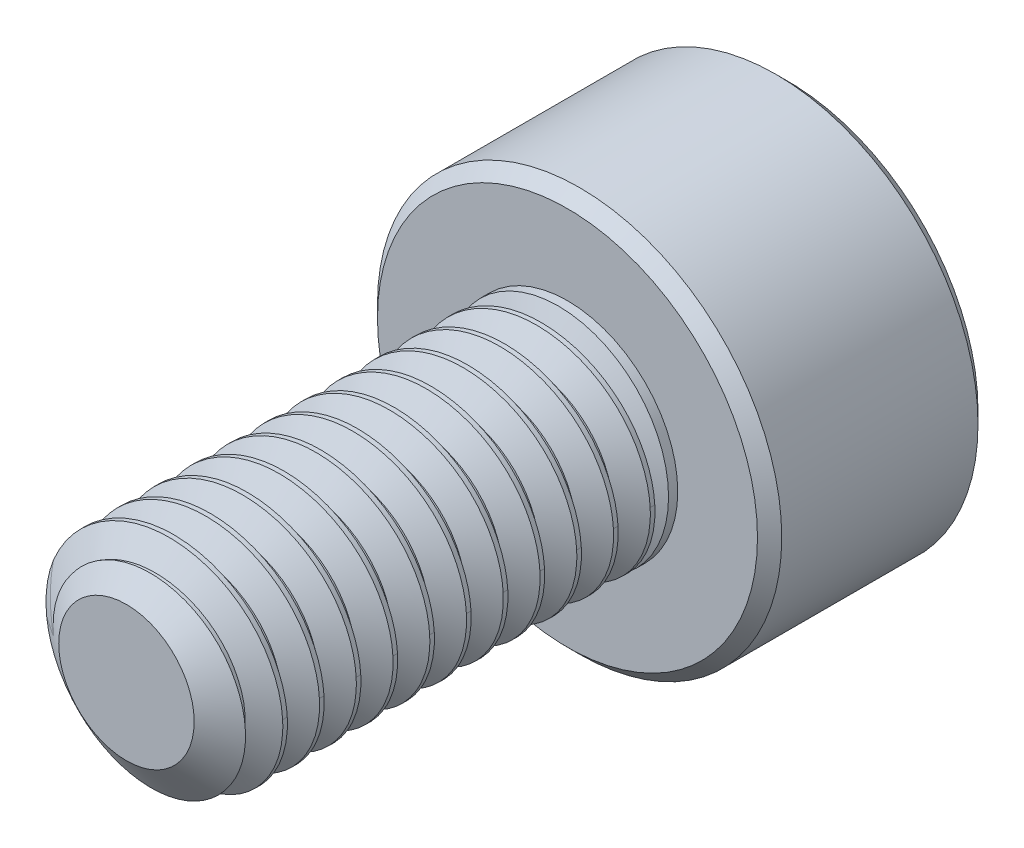
SolidWorks part; units mm, degrees
ref_plane "Front Plane" through (0, 0, 0) normal (0, 0, 1) x (1, 0, 0)
ref_plane "Top Plane" through (0, 0, 0) normal (0, 1, 0) x (1, 0, 0)
ref_plane "Right Plane" through (0, 0, 0) normal (1, 0, 0) x (0, 0, -1)
sketch "Sketch1" plane through (0, 0, 0) normal (0, 0, 1) x (1, 0, 0)
  circle A0 centre (0, 0) radius 1.5
  dimension "OD" = 3
extrude "Extrude1" add sketch "Sketch1" against normal blind 6
sketch "Sketch2" plane through (0, 0, 0) normal (0, 0, 1) x (1, 0, 0)
  circle A0 centre (0, 0) radius 1.5 construction
  circle A1 centre (0, 0) radius 1.5
curve "Helix/Spiral1" pitch 0.5 height 6.5 radius 1.5 centre (0, 0, 0) axis (0, 0, -1) start towards (0, 1, 0) parameters "pitch"=0.5
sketch "Sketch3" plane through (0, 0, 0) normal (1, 0, 0) x (0, 0, -1)
  line L0 (-0.4375, 1.5) -> (-0.25, 1.1752)
  line L1 (-0.25, 1.1752) -> (-0.1875, 1.1752)
  line L2 (-0.1875, 1.1752) -> (0, 1.5)
  line L3 (-0.4375, 1.5) -> (0, 1.5)
  line L4 (-0.2187, 1.5) -> (-0.2187, 1.1752) construction
  line L5 (-0.3437, 1.3376) -> (-0.0937, 1.3376) construction
  line L6 (0, 1.5) -> (0, -1.5) construction
  line L7 (0, -1.5) -> (6, -1.5) construction
  point P11 (2.25, -1.5)
  dimension "D1" = 0.0625
  dimension "D2" = 0.25
  dimension "D3" = 60
  dimension "D4" = 2.25
sweep "Cut-Sweep1" cut profiles "Sketch3" path "Helix/Spiral1"
sketch "Sketch4" plane through (0, 0, 0) normal (1, 0, 0) x (0, 0, -1)
  line L0 (0.4053, 1.5) -> (0, 0.9212)
  line L1 (0, 0.9212) -> (0, 1.5)
  line L2 (0.4053, 1.5) -> (0, 1.5)
  line L3 (-0.4375, 1.5) -> (0, 1.5) construction
  line L4 (0, 0) -> (7.0209, 0) construction
  dimension "D1" = 55
  dimension "D2" = 0.254
revolve "Cut-Revolve1" cut sketch "Sketch4" angle 360 about L4
sketch "Sketch5" plane through (0, 0, 0) normal (1, 0, 0) x (0, 0, -1)
  line L0 (6, -1.1822) -> (6, 1.0703) construction
  line L1 (6, 1.5) -> (0.1203, 1.5)
  line L2 (6, 1.5) -> (6, 0)
  line L3 (6, 0) -> (0.0001, 0)
  line L4 (0.0001, 1.1698) -> (0.0001, 0)
  line L5 (0.1203, 1.5) -> (0.0001, 1.1698)
  line L6 (0, 0) -> (9.9695, 0) construction
  point P3 (0.0001, 1.5)
  point P10 (0.0001, 1.5)
  dimension "D1" = 0.3302
  dimension "Thread min" = 0.0001
  dimension "D3" = 20
revolve "partially thread" [suppressed] add sketch "Sketch5" angle 360 about L6
sketch "Sketch6" plane through (0, 0, -6) normal (0, 0, -1) x (-1, 0, 0)
  circle A0 centre (0, 0) radius 2.75
  dimension "head dia" = 5.5
extrude "Extrude2" add sketch "Sketch6" along normal blind 3
sketch "Sketch7" plane through (0, 0, -9) normal (0, 0, -1) x (-1, 0, 0)
  line L1 (0, 1.4434) -> (-1.25, 0.7217)
  line L2 (-1.25, 0.7217) -> (-1.25, -0.7217)
  line L3 (-1.25, -0.7217) -> (0, -1.4434)
  line L4 (0, -1.4434) -> (1.25, -0.7217)
  line L5 (1.25, -0.7217) -> (1.25, 0.7217)
  line L6 (1.25, 0.7217) -> (0, 1.4434)
  circle A0 centre (0, 0) radius 1.25 construction
  dimension "hex dia" = 2.5
extrude "Cut-Extrude1" cut sketch "Sketch7" against normal blind 1.875
sketch "Sketch8" plane through (0, 0, -9) normal (0, 0, -1) x (-1, 0, 0)
  circle A0 centre (0, 0) radius 1.4434
extrude "Cut-Extrude2" cut sketch "Sketch8" against normal through all draft 45
chamfer "Chamfer1" distance 0.165 angle 45 2 edges at (-2.75, 0, -9) (-2.75, 0, -6)
sketch "Sketch9" plane through (0, 0, 0) normal (1, 0, 0) x (0, 0, -1)
  line L0 (0, 1.5) -> (0, -1.5) construction
  line L1 (2.75, 1.5) -> (2.75, -1.5) construction
  dimension "D1" = 2.75
sketch "Sketch10" plane through (0, 0, 0) normal (1, 0, 0) x (0, 0, -1)
  line L0 (6, 1.5) -> (6, 0)
  line L1 (6, 1.5) -> (5.875, 1.5)
  line L2 (5.875, 1.5) -> (5.2537, 0)
  line L3 (6, 0) -> (5.2537, 0)
  line L4 (6, 2.585) -> (6, -2.585) construction
  dimension "D1" = 22.5
  dimension "D2" = 0.125
revolve "Revolve1" add sketch "Sketch10" angle 360 about L3
equation "\"D3@Helix/Spiral1\" = \"screw length@Extrude1\"+\"pitch@Helix/Spiral1\""
equation "\"D1@Sketch3\" = \"pitch@Helix/Spiral1\"*.125"
equation "\"D2@Sketch3\" = \"pitch@Helix/Spiral1\"*.5"
equation "\"D1@Cut-Extrude1\" = \"hex dia@Sketch7\"*.75"
equation "\"D1@Chamfer1\" = \"head dia@Sketch6\"*.03"
equation "\"D1@Sketch9\" = \"pitch@Helix/Spiral1\"*5.5"
equation "\"D2@Sketch10\" = \"pitch@Helix/Spiral1\"*.25"
equation "\"D4@Sketch3\" = \"pitch@Helix/Spiral1\"*4.50"
